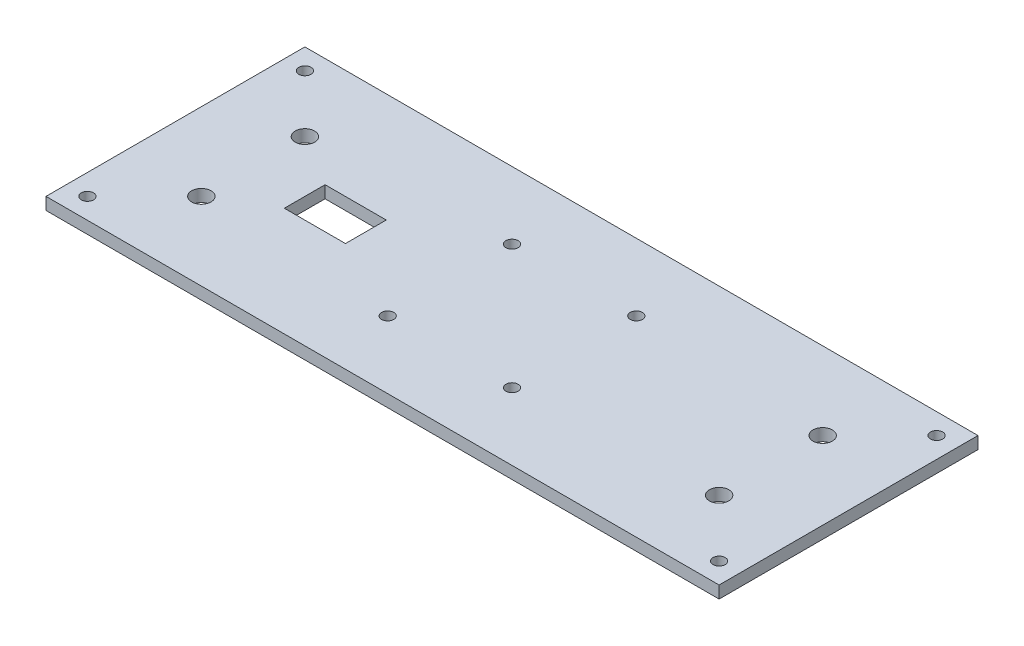
SolidWorks part; units mm, degrees
material "Thornel VCB-20 Carbon Cloth"
ref_plane "Front Plane" through (0, 0, 0) normal (0, 0, 1) x (1, 0, 0)
ref_plane "Top Plane" through (0, 0, 0) normal (0, 1, 0) x (1, 0, 0)
ref_plane "Right Plane" through (0, 0, 0) normal (1, 0, 0) x (0, 0, -1)
sketch "Sketch1" plane through (0, 0, 0) normal (0, 1, 0) x (1, 0, 0)
  line L0 (82.55, -31.75) -> (82.55, 31.75)
  line L1 (82.55, -31.75) -> (-82.55, -31.75)
  line L2 (82.55, 31.75) -> (-82.55, 31.75)
  line L3 (-82.55, -31.75) -> (-82.55, 31.75)
  line L4 (82.55, -31.75) -> (-82.55, 31.75) construction
  line L5 (82.55, 31.75) -> (-82.55, -31.75) construction
  point P1 (0, 0)
  dimension "D1" = 165.1
  dimension "D2" = 63.5
extrude "Boss-Extrude1" add sketch "Sketch1" along normal blind 3
sketch "Sketch6" plane through (0, 0, 0) normal (0, -1, 0) x (1, 0, 0)
  line L0 (-82.55, -31.75) -> (-82.55, 31.75) construction
  line L1 (-50.8, 5.047) -> (-35.8, 5.047)
  line L2 (-50.8, 5.047) -> (-50.8, -4.953)
  line L3 (-50.8, -4.953) -> (-35.8, -4.953)
  line L4 (-35.8, 5.047) -> (-35.8, -4.953)
  line L6 (82.55, -31.75) -> (-82.55, -31.75) construction
  circle A0 centre (-15.25, 15.25) radius 1.5
  circle A1 centre (15.25, 15.25) radius 1.5
  circle A2 centre (-15.25, -15.25) radius 1.5
  circle A3 centre (15.25, -15.25) radius 1.5
  dimension "D5" = 3
  dimension "D6" = 3
  dimension "D7" = 3
  dimension "D8" = 3
  dimension "D1" = 15
  dimension "D2" = 10
  dimension "D3" = 31.75
  dimension "D4" = 26.797
  dimension "D9" = 15.25
  dimension "D10" = 15.25
  dimension "D11" = 15.25
  dimension "D12" = 15.25
  dimension "D13" = 15.25
  dimension "D14" = 15.25
  dimension "D15" = 15.25
  dimension "D16" = 15.25
extrude "Cut-Extrude1" cut sketch "Sketch6" against normal up to next
sketch "Sketch7" plane through (0, 3, 0) normal (0, 1, 0) x (1, 0, 0)
  line L0 (-82.55, 31.75) -> (-82.55, -31.75) construction
  line L1 (82.55, -31.75) -> (82.55, 31.75) construction
  line L2 (-82.55, -31.75) -> (82.55, -31.75) construction
  line L3 (82.55, 31.75) -> (-82.55, 31.75) construction
  circle A0 centre (-77.47, 26.67) radius 1.5
  circle A1 centre (-77.47, -26.67) radius 1.5
  circle A2 centre (77.47, -26.67) radius 1.5
  circle A3 centre (77.47, 26.67) radius 1.5
  dimension "D9" = 3
  dimension "D10" = 3
  dimension "D11" = 3
  dimension "D12" = 3
  dimension "D1" = 5.08
  dimension "D2" = 5.08
  dimension "D3" = 5.08
  dimension "D4" = 5.08
  dimension "D5" = 5.08
  dimension "D6" = 5.08
  dimension "D7" = 5.08
  dimension "D8" = 5.08
extrude "Cut-Extrude2" cut sketch "Sketch7" against normal up to next
sketch "Sketch8" plane through (0, 3, 0) normal (0, 1, 0) x (1, 0, 0)
  line L0 (-82.55, -31.75) -> (82.55, -31.75) construction
  line L1 (-82.55, 31.75) -> (-82.55, -31.75) construction
  line L2 (82.55, -31.75) -> (82.55, 31.75) construction
  line L3 (82.55, 31.75) -> (-82.55, 31.75) construction
  circle A0 centre (-63.5, -12.7) radius 2.3813
  circle A1 centre (-63.5, 12.7) radius 2.3813
  circle A2 centre (63.5, 12.7) radius 2.3813
  circle A3 centre (63.5, -12.7) radius 2.3813
  dimension "D1" = 4.7625
  dimension "D4" = 4.7625
  dimension "D5" = 4.7625
  dimension "D6" = 4.7625
  dimension "D2" = 19.05
  dimension "D3" = 19.05
  dimension "D7" = 19.05
  dimension "D8" = 19.05
  dimension "D9" = 19.05
  dimension "D10" = 19.05
  dimension "D11" = 19.05
  dimension "D12" = 19.05
extrude "Cut-Extrude3" cut sketch "Sketch8" against normal up to next
